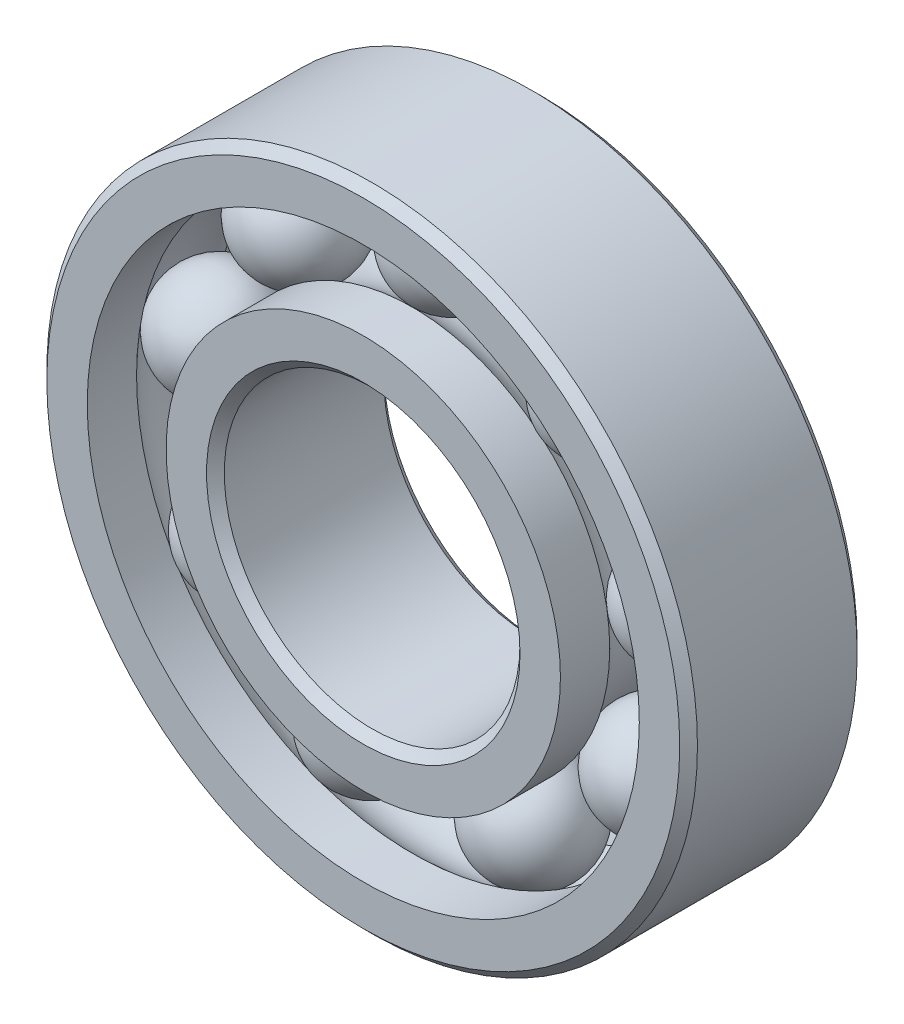
SolidWorks part; units mm, degrees
material "Plain Carbon Steel"
ref_plane "Front Plane" through (0, 0, 0) normal (0, 0, 1) x (1, 0, 0)
ref_plane "Top Plane" through (0, 0, 0) normal (0, 1, 0) x (1, 0, 0)
ref_plane "Right Plane" through (0, 0, 0) normal (1, 0, 0) x (0, 0, -1)
sketch "Sketch1" plane through (0, 0, 0) normal (0, 0, 1) x (1, 0, 0)
  circle A0 centre (0, 0) radius 11
  circle A1 centre (0, 0) radius 5
  dimension "ID" = 10
  dimension "OD" = 22
  dimension "For Shaft Diameter" = 10
  dimension "For Housing ID" = 22
sketch "Sketch5" plane through (0, 0, 0) normal (1, 0, 0) x (0, 0, -1)
  line L0 (-3, 0) -> (3, 0) construction
  line L1 (0, 11) -> (0, -11) construction
  line L2 (2.7, 11) -> (-2.7, 11)
  line L3 (-2.7, 11) -> (-3, 10.7)
  line L4 (-3, 10.7) -> (-3, 9.3333)
  line L5 (-3, 9.3333) -> (-1.3333, 9.3333)
  line L6 (3, 9.3333) -> (1.3333, 9.3333)
  line L7 (3, 10.7) -> (3, 9.3333)
  line L8 (2.7, 11) -> (3, 10.7)
  line L9 (0, 11) -> (0, 8) construction
  line L10 (0, 8) -> (0, 5) construction
  line L11 (-1.8856, 8) -> (-3, 8) construction
  line L12 (2.2523, 6.6921) -> (2.6333, 6.6921) construction
  line L13 (-2.2523, 6.6921) -> (-2.6333, 6.6921) construction
  line L14 (-2.2523, 6.6921) -> (-2.2523, 9.3079) construction
  line L15 (-2.2523, 9.3079) -> (-2.6333, 9.3079) construction
  line L16 (-2.6333, 6.6921) -> (-2.6333, 9.3079) construction
  line L17 (-2.2523, 6.6921) -> (-2.6333, 9.3079) construction
  line L18 (-2.2523, 9.3079) -> (-2.6333, 6.6921) construction
  line L19 (2.6333, 6.6921) -> (2.6333, 9.3079) construction
  line L20 (2.2523, 9.3079) -> (2.6333, 9.3079) construction
  line L21 (2.2523, 6.6921) -> (2.2523, 9.3079) construction
  line L22 (0, 11) -> (0, -11) construction
  arc A0 (-1.3333, 9.3333) -> (1.3333, 9.3333) centre (0, 8) cw
  circle A1 centre (0, 8) radius 1.8856 construction
  point P14 (0, 5)
  point P15 (-2.4428, 8)
  dimension "Width" = 6
  dimension "D1" = 45
  dimension "D2" = 0.3
  dimension "D3" = 2.6667
  dimension "D4" = 1.3333
  dimension "D5" = 0.381
  dimension "D6" = 0.0254
  dimension "D7" = 6
revolve "Revolve1" add sketch "Sketch5" angle 360 about L0
sketch "Sketch3" plane through (0, 0, 0) normal (1, 0, 0) x (0, 0, -1)
  line L0 (-3, 6.6667) -> (-1.3333, 6.6667)
  line L1 (0, 11) -> (0, -11) construction
  line L2 (-3, 10.7) -> (-3, 9.3333) construction
  line L3 (-3, 6.6667) -> (-3, 5.3)
  line L4 (-2.7, 11) -> (-3, 10.7) construction
  line L5 (-3, 5.3) -> (-2.7, 5)
  line L6 (-2.7, 5) -> (2.7, 5)
  line L7 (2.7, 11) -> (2.7, -11) construction
  line L8 (2.7, 5) -> (3, 5.3)
  line L9 (3, -10.7) -> (3, 10.7) construction
  line L10 (3, 5.3) -> (3, 6.6667)
  line L11 (3, 6.6667) -> (1.3333, 6.6667)
  line L13 (2.7, 11) -> (3, 10.7) construction
  arc A0 (1.3333, 9.3333) -> (-1.3333, 9.3333) centre (0, 8) ccw construction
  arc A1 (1.3333, 6.6667) -> (-1.3333, 6.6667) centre (0, 8) cw
revolve "Revolve3" add sketch "Sketch3" angle 360 about L0
sketch "Sketch4" plane through (0, 0, 0) normal (1, 0, 0) x (0, 0, -1)
  line L0 (-1.8856, 8) -> (1.8856, 8)
  arc A2 (-1.8856, 8) -> (1.8856, 8) centre (0, 8) cw
  arc A3 (1.3333, 9.3333) -> (-1.3333, 9.3333) centre (0, 8) ccw construction
revolve "Revolve4" add sketch "Sketch4" angle 360 about L0
pattern_circular "CirPattern1" count 9 every 40 of bodies 104
ref_axis "Center Axis 1" through (0, 0, -2.7) along (0, 0, 1)
equation "\"D2@Sketch5\" = \"Width@Sketch5\" * .05"
equation "\"D3@Sketch5\" = \"Width@Sketch5\" / 2.25"
equation "\"D4@Sketch5\"=((\"OD@Sketch1\"-\"ID@Sketch1\")/2)/4.5"
equation "\"D2@CirPattern1\" = 360/\"Balls@CirPattern1\""
